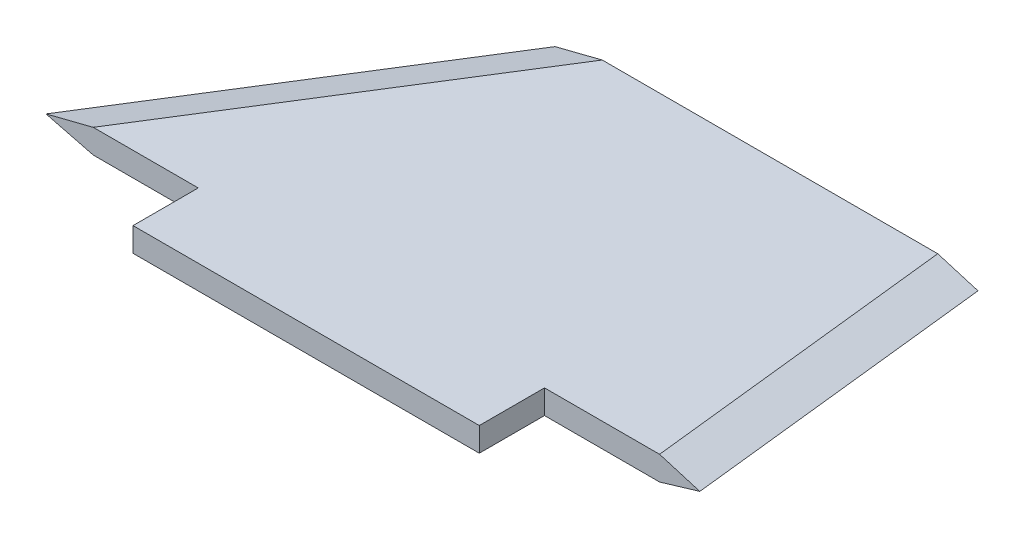
SolidWorks part; units mm, degrees
ref_plane "Front Plane" through (0, 0, 0) normal (0, 0, 1) x (1, 0, 0)
ref_plane "Top Plane" through (0, 0, 0) normal (0, 1, 0) x (1, 0, 0)
ref_plane "Right Plane" through (0, 0, 0) normal (1, 0, 0) x (0, 0, -1)
sketch "Sketch1" plane through (0, 0, 0) normal (0, 1, 0) x (1, 0, 0)
  line L0 (0, 0) -> (152.4, 0)
  line L1 (152.4, 0) -> (144.78, 68.834)
  line L2 (144.78, 68.834) -> (43.18, 68.834)
  line L3 (43.18, 68.834) -> (0, 0)
  dimension "D1" = 152.4
  dimension "D2" = 101.6
  dimension "D3" = 43.18
  dimension "D4" = 68.834
extrude "Boss-Extrude1" add sketch "Sketch1" along normal blind 5.2832
sketch "Sketch2" plane through (0, 0, 0) normal (0, 1, 0) x (1, 0, 0)
  line L0 (38.1, 0) -> (38.1, -14.351)
  line L1 (0, 0) -> (152.4, 0) construction
  line L2 (38.1, -14.351) -> (114.3, -14.351)
  line L3 (114.3, -14.351) -> (114.3, 0)
  line L4 (76.2, 0) -> (76.2, 68.834) construction
  line L5 (144.78, 68.834) -> (43.18, 68.834) construction
  line L6 (38.1, 0) -> (37.9252, -0.1232) construction
  line L7 (37.9252, -0.1232) -> (38.1, -0.1558) construction
  line L8 (43.18, 68.834) -> (0, 0)
  line L9 (0, 0) -> (152.4, 0)
  line L10 (152.4, 0) -> (144.78, 68.834)
  line L11 (144.78, 68.834) -> (43.18, 68.834)
  line L13 (38.1, 0) -> (114.3, 0)
  line L16 (76.2, -14.351) -> (76.2, 0) construction
  dimension "D1" = 76.2
  dimension "D2" = 14.351
  dimension "D3" = 14.351
  dimension "D6" = 0
extrude "Boss-Extrude2" add sketch "Sketch2" along normal blind 5.2832
chamfer "Chamfer1" distance 3.81 distance2 12.7 2 edges at (21.59, 0, -34.417) (21.59, 5.2832, -34.417) first distance on face at (21.59, 2.6416, -34.417)
chamfer "Chamfer2" distance 12.7 distance2 3.81 1 edges at (148.59, 0, -34.417) first distance on face at (84.393, 0, -13.6207)
chamfer "Chamfer3" distance 3.81 distance2 12.7 1 edges at (148.59, 5.2832, -34.417) first distance on face at (148.59, 4.5466, -34.417)
